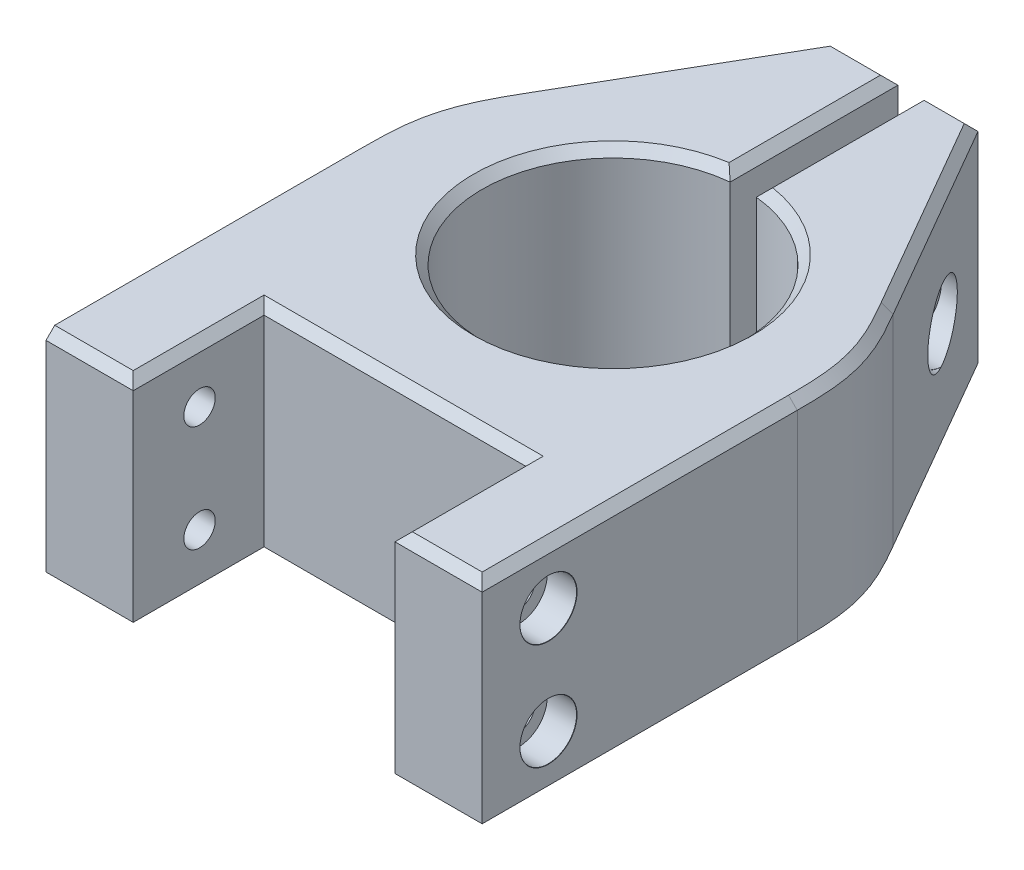
SolidWorks part; units mm, degrees
note: The reader was unsure of these and kept them because the rebuilt part matched: shared geometry of "Sketch6<3>".
material "ABS PC"
ref_plane "Front Plane" through (0, 0, 0) normal (0, 0, 1) x (1, 0, 0)
ref_plane "Top Plane" through (0, 0, 0) normal (0, 1, 0) x (1, 0, 0)
ref_plane "Right Plane" through (0, 0, 0) normal (1, 0, 0) x (0, 0, -1)
ref_plane "Plane1" through (13.5, 0, 0) normal (1, 0, 0) x (0, 0, -1)
sketch "Sketch1" plane through (0, 0, 0) normal (0, 1, 0) x (1, 0, 0)
  line L0 (0, -25) -> (15, -25)
  line L1 (15, -25) -> (15, -40)
  line L2 (15, -40) -> (25, -40)
  line L3 (25, -40) -> (25, 4.16)
  line L4 (25, 4.16) -> (7.6795, 34.16)
  line L5 (7.6795, 34.16) -> (1.5, 34.16)
  line L6 (1.5, 34.16) -> (1.5, 14.9248)
  line L7 (0, -25) -> (0, -15)
  line L8 (0, -15) -> (0, 0) construction
  arc A0 (0, -15) -> (1.5, 14.9248) centre (0, 0) ccw
  dimension "D1" = 30
  dimension "D6" = 19.16
  dimension "D2" = 30
  dimension "D3" = 50
  dimension "D4" = 15
  dimension "D5" = 10
  dimension "D7" = 1.5
  dimension "D8" = 150
  dimension "D9" = 30
extrude "Boss-Extrude1" add sketch "Sketch1" along normal blind 25
mirror "Mirror1" about plane through (0, 25, 25) normal (1, 0, 0) of bodies 101
fillet "Fillet1" radius 30 2 edges at (-25, 12.5, -4.16) (25, 12.5, -4.16)
chamfer "Chamfer1" distance 1 angle 45 2 edges at (0, 0, 15) (0, 25, 15)
sketch "Sketch2" plane through (-25, 0, 0) normal (-1, 0, 0) x (0, 0, 1)
  line L0 (40, 25) -> (40, 0) construction
  line L5 (32.4, 18.6) -> (32.4, 25) construction
  line L6 (40, 25) -> (3.8785, 25) construction
  line L7 (32.4, 6.4) -> (32.4, 0) construction
  line L8 (40, 0) -> (3.8785, 0) construction
  circle A0 centre (32.4, 18.6) radius 1.6
  circle A1 centre (32.4, 6.4) radius 1.6
  dimension "D1" = 3.2
  dimension "D2" = 6
  dimension "D3" = 9
sketch "Sketch6" plane through (0, 0, 0) normal (1, 0, 0) x (0, 0, -1)
  line L1 (24.5424, 0) -> (24.5424, 25) construction
  line L2 (14.9248, 12.5) -> (34.16, 12.5) construction
  line L3 (34.16, 25) -> (15.9295, 25) construction
  line L4 (34.16, 25) -> (34.16, 0) construction
  line L5 (34.16, 0) -> (15.9295, 0) construction
  line L6 (14.9248, 24) -> (14.9248, 1) construction
  circle A0 centre (24.5424, 12.5) radius 1
  circle A1 centre (24.5424, 12.5) radius 1.5
  point P5 (24.5424, 12.5)
  point P9 (24.5424, 12.5)
  dimension "D1" = 2
  dimension "D2" = 3
extrude "Cut-Extrude2" cut sketch "Sketch6" against normal through all both and the other way through all contours A0
extrude "Cut-Extrude3" cut sketch "Sketch6<3>" against normal up to surface (0.3662 mm away) from offset 12 contours A1
sketch "Sketch6<3>" plane through (0, 0, 0) normal (1, 0, 0) x (0, 0, -1) same geometry as "Sketch6"
chamfer "Chamfer2" distance 1 angle 45 27 edges at (-1.5, 0, -25.0448) (-4.5897, 0, -34.16) (4.5897, 0, -34.16) (4.5897, 25, -34.16) (1.5, 0, -25.0448) (-20, 0, 40) (-15, 0, 32.5) (0, 0, 25) (0, 25, 25) (15, 0, 32.5) (15, 25, 32.5) (20, 0, 40) (20, 25, 40) (1.5, 25, -25.0448) (-1.5, 25, -25.0448) (-4.5897, 25, -34.16) (-20, 25, 40) (-15, 25, 32.5)
sketch "Sketch7" plane through (-1.5, 0, 0) normal (1, 0, 0) x (0, 0, -1)
  line L1 (24.5424, 8.3431) -> (28.1424, 10.4215)
  line L2 (28.1424, 10.4215) -> (28.1424, 14.5785)
  line L3 (28.1424, 14.5785) -> (24.5424, 16.6569)
  line L4 (24.5424, 16.6569) -> (20.9424, 14.5785)
  line L5 (20.9424, 14.5785) -> (20.9424, 10.4215)
  line L6 (20.9424, 10.4215) -> (24.5424, 8.3431)
  circle A0 centre (24.5424, 12.5) radius 3.6 construction
  dimension "D1" = 7.2
extrude "Cut-Extrude4" cut sketch "Sketch7" against normal through all from offset 6 offset against normal yes
chamfer "Chamfer4" distance 0.5 angle 45 6 edges at (-12.193, 9.3823, -26.3424) (-11.1538, 12.5, -28.1424) (-12.193, 15.6177, -26.3424) (-14.2714, 15.6177, -22.7424) (-15.3107, 12.5, -20.9424) (-14.2714, 9.3823, -22.7424)
hole_wizard "CBORE for M3 Hex Socket Head Cap Screw1" positions "Sketch8" profile "Sketch9" counterbore size "M3" standard "ISO" end condition up to next
sketch "Sketch8" plane through (25, 0, 0) normal (1, 0, 0) x (0, 0, -1)
  point P0 (-32.4, 18.6)
  point P3 (-32.4, 6.4)
sketch "Sketch9" plane through (25, 18.6, 32.4) normal (0, 1, 0) x (0, 0, -1)
  line L0 (0, 0) -> (0, 10)
  line L1 (0, 10) -> (1.8, 10)
  line L3 (1.8, 10) -> (1.8, 3.4)
  line L4 (3.25, 3.4) -> (1.8, 3.4)
  line L5 (3.25, 3.4) -> (3.25, 0.025)
  line L6 (3.25, 0.025) -> (3.275, 0)
  line L7 (3.275, 0) -> (0, 0)
  line L8 (-3.25, 0.025) -> (-3.275, 0) construction
  line L11 (0, -6.35) -> (0, 107.95) construction
  dimension "Thru Hole Dia." = 3.6
  dimension "Thru Hole Depth" = 10
  dimension "C'Bore Dia." = 6.5
  dimension "C'Bore Depth" = 3.4
  dimension "Near C'Sink Dia." = 6.55
  dimension "Near C'Sink Angle" = 90
hole_wizard "CBORE for M3 Hex Socket Head Cap Screw2" positions "Sketch10" profile "Sketch11" counterbore size "M3" standard "ISO" end condition up to next
sketch "Sketch10" plane through (-25, 0, 0) normal (-1, 0, 0) x (0, 0, 1)
  point P0 (32.4, 18.6)
  point P3 (32.4, 6.4)
sketch "Sketch11" plane through (-25, 18.6, 32.4) normal (0, 1, 0) x (0, 0, 1)
  line L0 (0, 0) -> (0, 10)
  line L1 (0, 10) -> (1.8, 10)
  line L3 (1.8, 10) -> (1.8, 3.4)
  line L4 (3.25, 3.4) -> (1.8, 3.4)
  line L5 (3.25, 3.4) -> (3.25, 0.025)
  line L6 (3.25, 0.025) -> (3.275, 0)
  line L7 (3.275, 0) -> (0, 0)
  line L8 (-3.25, 0.025) -> (-3.275, 0) construction
  line L11 (0, -6.35) -> (0, 107.95) construction
  dimension "Thru Hole Dia." = 3.6
  dimension "Thru Hole Depth" = 10
  dimension "C'Bore Dia." = 6.5
  dimension "C'Bore Depth" = 3.4
  dimension "Near C'Sink Dia." = 6.55
  dimension "Near C'Sink Angle" = 90
hole_wizard "CBORE for M4 Hex Socket Head Cap Screw1" positions "Sketch12" profile "Sketch13" counterbore size "M4" standard "ISO"
sketch "Sketch12" plane through (13.5, 0, 0) normal (1, 0, 0) x (0, 0, -1)
  point P0 (24.5424, 12.5)
sketch "Sketch13" plane through (13.5, 12.5, -24.5424) normal (0, 1, 0) x (0, 0, -1)
  line L0 (0, 0) -> (0, 22.3519)
  line L1 (0, 22.3519) -> (2.25, 21)
  line L2 (2.25, 21) -> (2.25, 4.4)
  line L3 (2.25, 4.4) -> (4, 4.4)
  line L5 (4, 4.4) -> (4, 0.025)
  line L6 (4, 0.025) -> (4.025, 0)
  line L7 (4.025, 0) -> (0, 0)
  line L8 (-4, 0.025) -> (-4.025, 0) construction
  line L10 (0, 22.3519) -> (-2.25, 21) construction
  line L11 (0, -6.35) -> (0, 107.95) construction
  dimension "Hole Dia." = 4.5
  dimension "Hole Depth" = 21
  dimension "C'Bore Dia." = 8
  dimension "C'Bore Depth" = 4.4
  dimension "Near C'Sink Dia." = 8.05
  dimension "Near C'Sink Angle" = 90
  dimension "Drill Angle" = 118
sketch "Sketch14" plane through (9.1, 0, 0) normal (1, 0, 0) x (0, 0, -1)
  circle A0 centre (24.5424, 12.5) radius 4 construction
  circle A1 centre (24.5424, 12.5) radius 4
extrude "Cut-Extrude5" cut sketch "Sketch14" along normal through all
